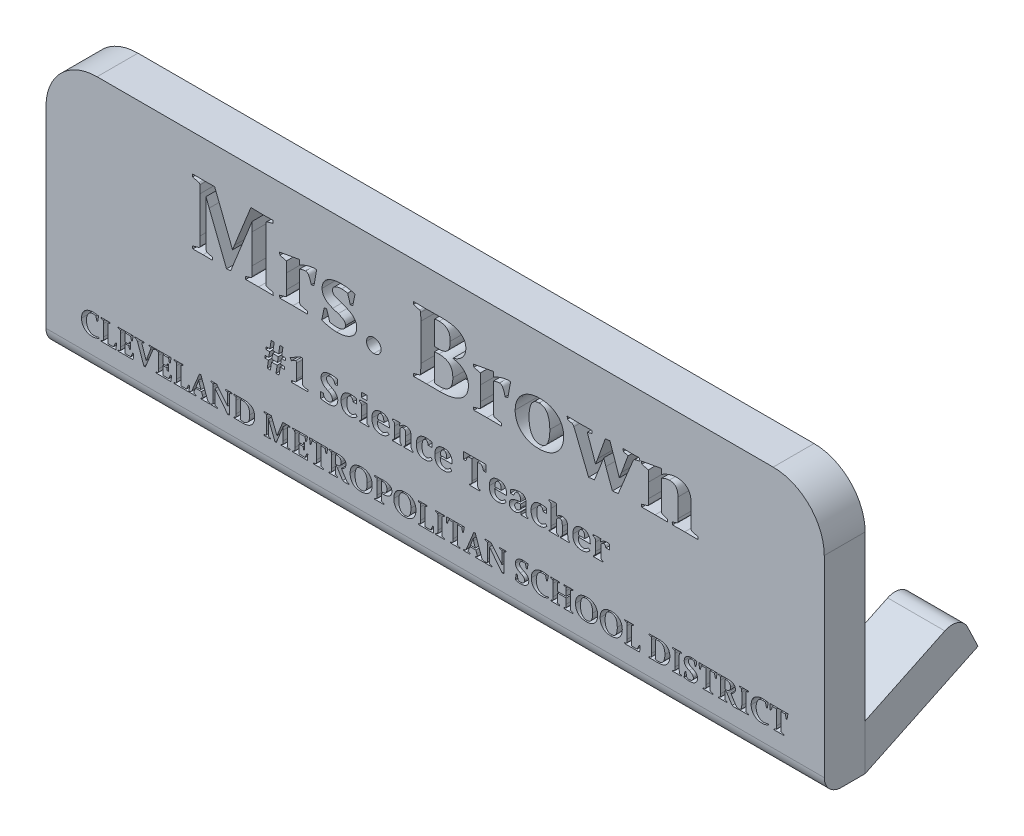
SolidWorks part; units mm, degrees
ref_plane "Front Plane" through (0, 0, 0) normal (0, 0, 1) x (1, 0, 0)
ref_plane "Top Plane" through (0, 0, 0) normal (0, 1, 0) x (1, 0, 0)
ref_plane "Right Plane" through (0, 0, 0) normal (1, 0, 0) x (0, 0, -1)
sketch "Sketch1" plane through (0, 0, 0) normal (0, 0, 1) x (1, 0, 0)
  line L1 (-108.803, -40.1851) -> (119.797, -40.1851)
  line L2 (-108.803, -40.1851) -> (-108.803, 21.3149)
  line L3 (-93.803, 36.3149) -> (104.797, 36.3149)
  line L4 (119.797, -40.1851) -> (119.797, 21.3149)
  arc A0 (104.797, 36.3149) -> (119.797, 21.3149) centre (104.797, 21.3149) cw
  arc A1 (-108.803, 21.3149) -> (-93.803, 36.3149) centre (-93.803, 21.3149) cw
  point P6 (119.797, 36.3149)
  dimension "D3" = 15
  dimension "D1" = 228.6
  dimension "D2" = 76.5
extrude "Boss-Extrude1" add sketch "Sketch1" along normal blind 12
sketch "Sketch2" plane through (119.797, 0, 0) normal (1, 0, 0) x (0, 0, -1)
  line L0 (0, -40.1851) -> (33.1567, -24.3437)
  line L1 (33.1567, -24.3437) -> (27.9311, -13.4062)
  line L2 (27.9311, -13.4062) -> (0, -26.7509)
  line L3 (0, -40.1851) -> (0, 21.3149) construction
  line L4 (0, -26.7509) -> (0, -40.1851)
extrude "Boss-Extrude2" add sketch "Sketch2" along normal blind 0.001 and the other way blind 228.6
sketch "Sketch3" plane through (0, -32.7169, -15.6312) normal (0, -0.9023, -0.4311) x (1, 0, 0)
  line L0 (-108.803, 17.3237) -> (119.797, 17.3237) construction
  line L1 (-92.003, 17.3237) -> (102.997, 17.3237)
  line L2 (-92.003, 17.3237) -> (-92.003, -19.423)
  line L3 (-92.003, -19.423) -> (102.997, -19.423)
  line L4 (102.997, 17.3237) -> (102.997, -19.423)
  line L5 (-108.803, -19.423) -> (119.798, -19.423) construction
  line L6 (-108.803, 17.3237) -> (-108.803, -19.423) construction
  line L7 (119.797, 17.3237) -> (119.798, -19.423) construction
  dimension "D1" = 195
  dimension "D2" = 16.8
  dimension "D3" = 16.8
extrude "Cut-Extrude1" cut sketch "Sketch3" against normal blind 13
fillet "Fillet2" radius 5 1 edges at (5.497, -40.1851, 12)
fillet "Fillet3" radius 5 1 edges at (5.497, -28.4551, 5.6043)
sketch "Sketch4" plane through (0, 0, 12) normal (0, 0, 1) x (1, 0, 0)
  text T0 "Mrs. Brown" font "Constantia" height in points 72
extrude "Cut-Extrude2" cut sketch "Sketch4" against normal blind 7
sketch "Sketch5" plane through (0, 0, 12) normal (0, 0, 1) x (1, 0, 0)
  text T0 "CLEVELAND METROPOLITAN SCHOOL DISTRICT" font "Constantia" height in points 23
extrude "Cut-Extrude3" cut sketch "Sketch5" against normal blind 7
fillet "Fillet4" radius 5 2 edges at (-100.403, -13.4062, -27.9311) (111.3975, -13.4062, -27.9311)
sketch "Sketch6" plane through (0, 0, 12) normal (0, 0, 1) x (1, 0, 0)
  text T0 "#1 Science Teacher" font "Cambria" height in points 28
extrude "Cut-Extrude4" cut sketch "Sketch6" against normal blind 7
sketch "Sketch8" plane through (0, -32.7169, -15.6312) normal (0, -0.9023, -0.4311) x (1, 0, 0)
  text T0 "NS" font "Dutch801 Rm BT" height in points 26
extrude "Cut-Extrude5" cut sketch "Sketch8" against normal blind 5
